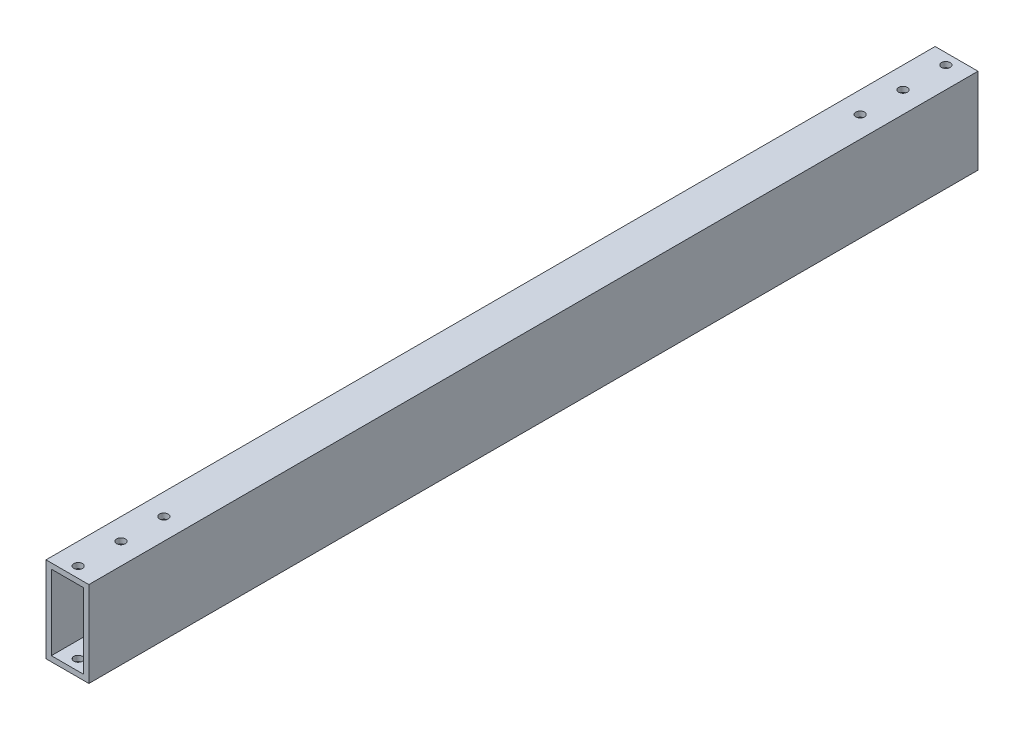
SolidWorks part; units mm, degrees
material "6061-T6 (SS)"
ref_plane "Front" through (0, 0, 0) normal (0, 0, 1) x (1, 0, 0)
ref_plane "Top" through (0, 0, 0) normal (0, 1, 0) x (1, 0, 0)
ref_plane "Right" through (0, 0, 0) normal (1, 0, 0) x (0, 0, -1)
sketch "Sketch1" plane through (0, 0, 0) normal (0, 0, 1) x (1, 0, 0)
  line L1 (-12.7, -25.4) -> (12.7, -25.4)
  line L2 (-12.7, -25.4) -> (-12.7, 25.4)
  line L3 (-12.7, 25.4) -> (12.7, 25.4)
  line L4 (12.7, -25.4) -> (12.7, 25.4)
  line L5 (-12.7, -25.4) -> (12.7, 25.4) construction
  line L6 (-12.7, 25.4) -> (12.7, -25.4) construction
  point P0 (0, 0)
  dimension "D1" = 25.4
  dimension "D2" = 50.8
extrude "Extrude-Thin1" add sketch "Sketch1" along normal blind 527.05 thin thin type one direction reverse wall 3.175
hole_wizard "#10 Clearance Hole1" positions "Sketch2" profile "Sketch3" hole size "#10" standard "ANSI Inch" end condition through all
sketch "Sketch2" plane through (0, 25.4, 0) normal (0, 1, 0) x (1, 0, 0)
  line L0 (12.7, -527.05) -> (-12.7, -527.05) construction
  line L1 (-12.7, -527.05) -> (-12.7, 0) construction
  point P0 (0, -520.7)
  point P2 (0, -495.3)
  point P4 (0, -469.9)
  point P13 (0, -6.35)
  point P15 (0, -31.75)
  point P17 (0, -57.15)
  dimension "D1" = 6.35
  dimension "D2" = 25.4
  dimension "D3" = 25.4
  dimension "D4" = 12.7
  dimension "D5" = 6.35
  dimension "D6" = 25.4
  dimension "D7" = 25.4
sketch "Sketch3" plane through (0, 25.4, 520.7) normal (1, 0, 0) x (0, 0, 1)
  line L0 (0, 0) -> (0, 50.8)
  line L1 (0, 50.8) -> (2.5527, 50.8)
  line L2 (2.5527, 50.8) -> (2.5527, 0)
  line L5 (2.5527, 0) -> (0, 0)
  line L11 (0, -6.35) -> (0, 107.95) construction
  dimension "Thru Hole Dia." = 5.1054
  dimension "Thru Hole Depth" = 50.8
sketch "Sketch8" plane through (0, -25.4, 0) normal (0, -1, 0) x (-1, 0, 0)
  point P0 (3.175, -451.358)
  point P3 (-3.175, -425.958)
  point P6 (3.175, -400.558)
  point P9 (-3.175, -375.158)
  point P12 (3.175, -349.758)
  point P19 (3.175, -298.958)
  point P26 (3.175, -248.158)
  point P29 (-3.175, -222.758)
  point P32 (3.175, -197.358)
  point P35 (-3.175, -171.958)
  point P38 (3.175, -146.558)
  point P41 (-3.175, -121.158)
  point P48 (-3.175, -70.358)
  point P55 (-3.175, -324.358)
  point P58 (-3.175, -273.558)
  point P61 (3.175, -95.758)
hole_wizard "1/8 (0.13) Diameter Hole1" positions "Sketch8" profile "Sketch7" hole size "1/8" standard "ANSI Inch" end condition up to next
sketch "Sketch7" plane through (-3.175, -25.4, 451.358) normal (1, 0, 0) x (0, 0, -1)
  line L0 (0, 0) -> (0, 3.175)
  line L1 (0, 3.175) -> (1.651, 3.175)
  line L2 (1.651, 3.175) -> (1.651, 0)
  line L5 (1.651, 0) -> (0, 0)
  line L11 (0, -6.35) -> (0, 107.95) construction
  dimension "Thru Hole Dia." = 3.302
  dimension "Thru Hole Depth" = 3.175
